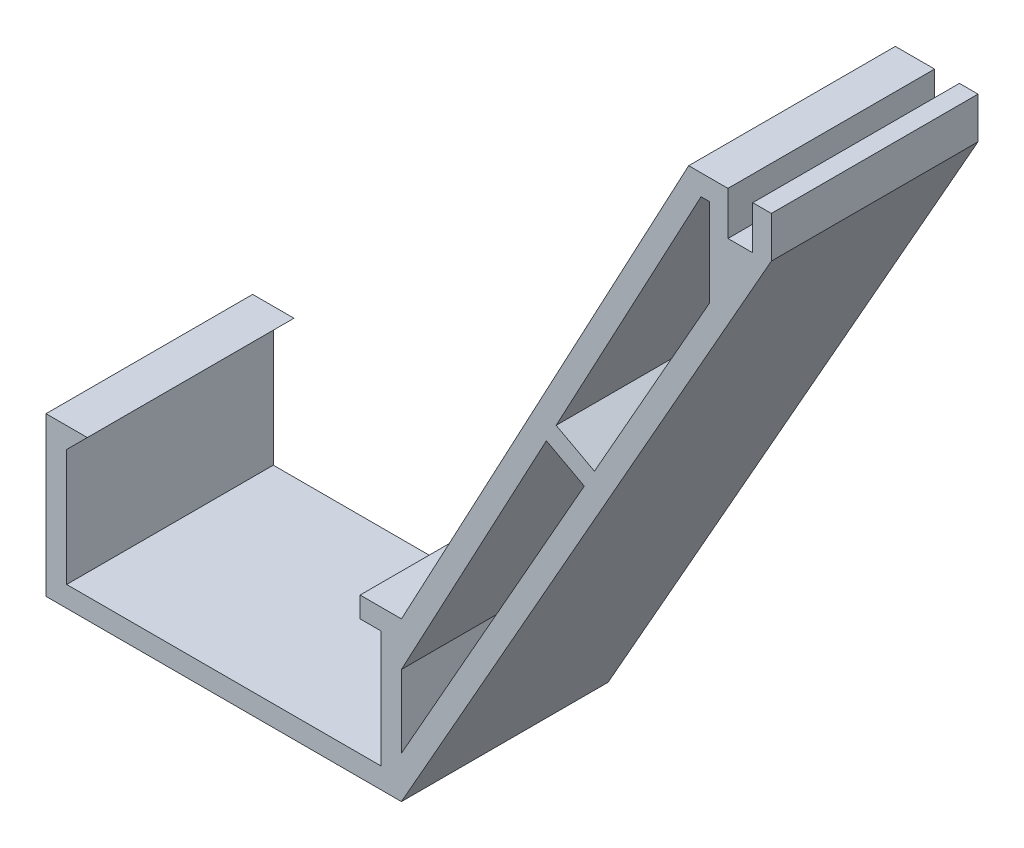
SolidWorks part; units mm, degrees
ref_plane "Front Plane" through (0, 0, 0) normal (0, 0, 1) x (1, 0, 0)
ref_plane "Top Plane" through (0, 0, 0) normal (0, 1, 0) x (1, 0, 0)
ref_plane "Right Plane" through (0, 0, 0) normal (1, 0, 0) x (0, 0, -1)
sketch "Sketch1" plane through (0, 0, 0) normal (0, 0, 1) x (1, 0, 0)
  line L0 (-15, 4.085) -> (-15, 15) construction
  line L1 (15, -15) -> (-15, -15) construction
  line L2 (15, -15) -> (15, -4.085) construction
  line L3 (15, 15) -> (-15, 15) construction
  line L4 (-15, -15) -> (-15, -4.085) construction
  line L5 (15, -15) -> (-15, 15) construction
  line L6 (15, 15) -> (-15, -15) construction
  line L7 (-15, 4.085) -> (-10, 4.085) construction
  line L9 (-15, -4.085) -> (-10, -4.085) construction
  line L10 (-10, 4.085) -> (-10, -4.085) construction
  line L11 (15, -4.085) -> (10, -4.085) construction
  line L13 (15, 4.085) -> (10, 4.085) construction
  line L14 (10, -4.085) -> (10, 4.085) construction
  line L15 (15, 4.085) -> (15, 15) construction
  line L16 (-15.2, -15.2) -> (-15.2, -3.885)
  line L25 (15.2, -3.885) -> (13.2, -3.885)
  line L26 (15.2, -15.2) -> (15.2, -3.885)
  line L27 (15.2, -15.2) -> (-15.2, -15.2)
  line L28 (-10.2, 3.885) -> (-10.2, -3.885) construction
  line L29 (-15.2, 3.885) -> (-10.2, 3.885) construction
  line L30 (-15.2, 3.885) -> (-15.2, 15.2) construction
  line L31 (15.2, 15.2) -> (-15.2, 15.2) construction
  line L32 (15.2, 3.885) -> (15.2, 15.2) construction
  line L33 (15.2, 3.885) -> (10.2, 3.885) construction
  line L34 (10.2, -3.885) -> (10.2, 3.885) construction
  line L35 (17.2, -1.885) -> (13.2, -1.885)
  line L36 (17.2, -17.2) -> (17.2, -1.885)
  line L37 (17.2, -17.2) -> (-17.2, -17.2)
  line L38 (-17.2, -17.2) -> (-17.2, -1.885)
  line L39 (-17.2, -1.885) -> (-13.2, -1.885)
  line L40 (13.2, -1.885) -> (13.2, -3.885)
  line L41 (-15.2, -3.885) -> (-13.2, -1.885)
  line L42 (-17.2, -1.885) -> (-10.2, -1.885) construction
  line L43 (-15.2, -3.885) -> (-10.2, -3.885) construction
  line L44 (17.2, -1.885) -> (10.2, -1.885) construction
  line L45 (15.2, -3.885) -> (10.2, -3.885) construction
  point P0 (0, 0)
  point P14 (-10, 0)
  point P15 (10, 0)
  dimension "D1" = 30
  dimension "D2" = 30
  dimension "D3" = 8.17
  dimension "D4" = 5
  dimension "D7" = 2
  dimension "D8" = 225
  dimension "D5" = 0.2
  dimension "D6" = 2
extrude "Boss-Extrude1" add sketch "Sketch1" along normal blind 20
sketch "Sketch2" plane through (0, 0, 0) normal (0, 0, -1) x (-1, 0, 0)
  line L0 (-15, -4.085) -> (-45, 50) construction
  line L1 (-45, 50) -> (-48.8, 50) construction
  line L2 (-51, 50) -> (-51, 86) construction
  line L3 (-51, 86) -> (-45, 86) construction
  line L4 (-45, 86) -> (-45, 84) construction
  line L5 (-45, 84) -> (-49, 84) construction
  line L6 (-49, 84) -> (-49, 52) construction
  line L7 (-49, 52) -> (-45, 52) construction
  line L8 (-45, 52) -> (-45, 50) construction
  line L9 (-51, 50) -> (-51, 46) construction
  line L10 (-51, 46) -> (-49, 46) construction
  line L11 (-49, 46) -> (-49, 50) construction
  line L12 (-45, 50) -> (-17.2, -1.885)
  line L13 (-45, 50) -> (-48.8, 50)
  line L14 (-53, 50) -> (-53, 46)
  line L15 (-53, 46) -> (-17.2, -17.2)
  line L16 (-17.2, -1.885) -> (-17.2, -6.1198)
  line L17 (-46.1974, 48) -> (-32.171, 21.8216)
  line L19 (-47, 39.4657) -> (-35.8798, 19.8344)
  line L22 (-46.1974, 48) -> (-51, 48) construction
  line L23 (-51, 46.5271) -> (-19.2, -9.6114) construction
  line L24 (-51, 48) -> (-51, 46.5271) construction
  line L25 (-46.1974, 48) -> (-47, 48)
  line L26 (-47, 48) -> (-47, 39.4657)
  line L27 (-46.1974, 48) -> (-19.2, -2.387) construction
  line L28 (-19.2, -2.387) -> (-19.2, -9.6114) construction
  line L29 (-17.2, -13.1422) -> (-17.2, -17.2)
  line L30 (-17.2, -1.885) -> (-17.2, -17.2) construction
  line L31 (-51.2, 50) -> (-51.2, 45.8)
  line L32 (-51.2, 45.8) -> (-48.8, 45.8)
  line L33 (-48.8, 45.8) -> (-48.8, 50)
  line L34 (-51.2, 50) -> (-53, 50)
  line L35 (-45, 50) -> (-53, 50) construction
  line L36 (-31.6987, 20.9401) -> (-35.3867, 18.9641) construction
  line L37 (-32.171, 21.8216) -> (-35.8798, 19.8344)
  line L38 (-31.2264, 20.0587) -> (-34.8937, 18.0937)
  line L39 (-32.171, 21.8216) -> (-35.859, 19.8455) construction
  line L40 (-31.2264, 20.0587) -> (-34.9145, 18.0826) construction
  line L41 (-34.8937, 18.0937) -> (-17.2, -13.1422)
  line L42 (-31.2264, 20.0587) -> (-17.2, -6.1198)
  line L43 (-31.6987, 20.9401) -> (-35.3867, 18.9641) construction
  dimension "D1" = 30
  dimension "D2" = 35
  dimension "D3" = 32
  dimension "D4" = 2
  dimension "D5" = 2
  dimension "D6" = 2
  dimension "D7" = 4
  dimension "D8" = 4
  dimension "D9" = 2
  dimension "D11" = 2
  dimension "D10" = 2
  dimension "D12" = 0.2
  dimension "D13" = 1
  dimension "D14" = 1
extrude "Boss-Extrude2" add sketch "Sketch2" against normal up to surface (20 mm away) up to face at (1.2, -7.6359, 20)
sketch "Sketch3" [suppressed] plane through (0, 0, 0) normal (0, 0, -1) x (-1, 0, 0)
  line L0 (-53, 50) -> (-53, 46) construction
  line L1 (-53, 50) -> (-65, 50)
  line L2 (-53, 50) -> (-53, 46)
  line L3 (-53, 46) -> (-65, 46)
  line L4 (-65, 50) -> (-65, 46)
  line L5 (-53, 46) -> (-17.2, -17.2) construction
  dimension "D1" = 12
extrude "Boss-Extrude3" [suppressed] add sketch "Sketch3" against normal up to surface (20 mm away) up to face at (25.13, 4.7226, 20)
sketch "Sketch4" [suppressed] plane through (0, 50, 0) normal (0, 1, 0) x (1, 0, 0)
  line L0 (59, -20) -> (59, 0) construction
  line L2 (51.2, 0) -> (65, 0) construction
  line L3 (65, -20) -> (65, 0) construction
  line L4 (65, -20) -> (51.2, -20) construction
  circle A0 centre (59, -10) radius 3.15
  dimension "D1" = 6.3
  dimension "D2" = 6
extrude "Cut-Extrude1" [suppressed] cut sketch "Sketch4" against normal up to next
